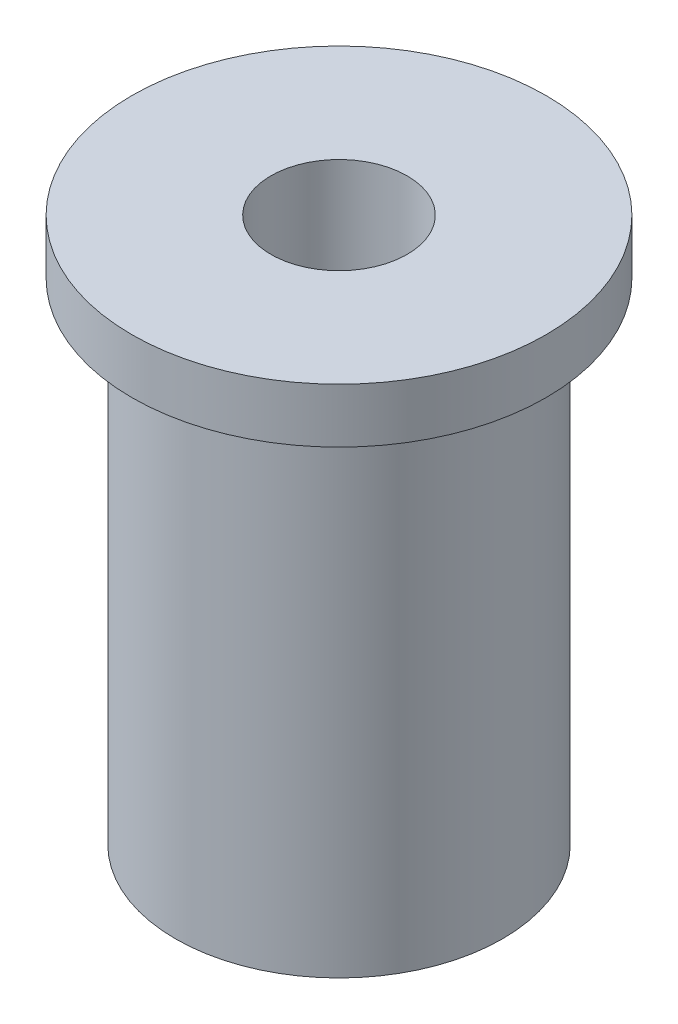
SolidWorks part; units mm, degrees
ref_plane "Front Plane" through (0, 0, 0) normal (0, 0, 1) x (1, 0, 0)
ref_plane "Top Plane" through (0, 0, 0) normal (0, 1, 0) x (1, 0, 0)
ref_plane "Right Plane" through (0, 0, 0) normal (1, 0, 0) x (0, 0, -1)
sketch "Sketch1" plane through (0, 0, 0) normal (1, 0, 0) x (0, 0, -1)
  line L0 (0, 0) -> (0, 12.3422) construction
  line L1 (1.25, 0) -> (1.25, 10)
  line L2 (1.25, 10) -> (3.8, 10)
  line L3 (3.8, 10) -> (3.8, 9)
  line L4 (3.8, 9) -> (3, 9)
  line L5 (3, 9) -> (3, 0)
  line L6 (3, 0) -> (1.25, 0)
  dimension "D1" = 1
  dimension "D2" = 9
  dimension "D3" = 1.25
  dimension "D4" = 3
  dimension "D5" = 3.8
revolve "Revolve1" add sketch "Sketch1" angle 360 about L0
